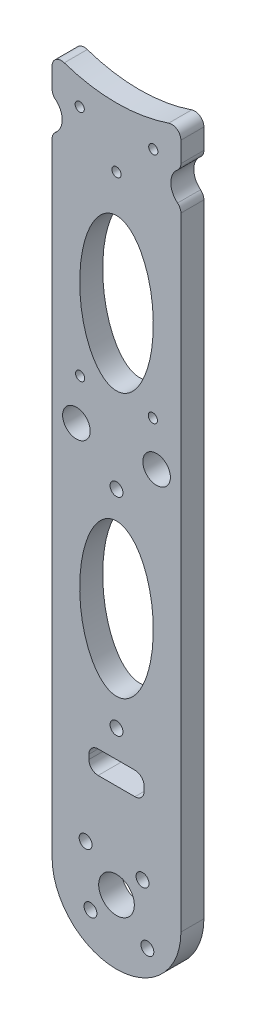
SolidWorks part; units mm, degrees
ref_plane "Front Plane" through (0, 0, 0) normal (0, 0, 1) x (1, 0, 0)
ref_plane "Top Plane" through (0, 0, 0) normal (0, 1, 0) x (1, 0, 0)
ref_plane "Right Plane" through (0, 0, 0) normal (1, 0, 0) x (0, 0, -1)
sketch "Sketch1" plane through (0, 0, 0) normal (0, 0, 1) x (1, 0, 0)
  line L0 (-14, 0) -> (-14, 135.3474)
  line L1 (0, 149.0732) -> (0, -14) construction
  line L2 (14, 0) -> (14, 135.3474)
  line L3 (-14, 0) -> (14, 0) construction
  line L4 (-6.7175, 6.7175) -> (6.7175, -6.7175) construction
  line L6 (-9.9779, -9.9779) -> (8.2462, 8.2462) construction
  line L7 (-14, 144.6611) -> (-14, 149.0732)
  line L8 (-4, 20.4839) -> (4, 20.4839)
  line L9 (-6, 22.4839) -> (-6, 23.4839)
  line L10 (-4, 25.4839) -> (4, 25.4839)
  line L11 (6, 22.4839) -> (6, 23.4839)
  line L12 (-6, 20.4839) -> (6, 25.4839) construction
  line L13 (-6, 25.4839) -> (6, 20.4839) construction
  line L14 (14, 144.6611) -> (14, 149.0732)
  arc A0 (-14, 0) -> (14, 0) centre (0, 0) ccw
  arc A1 (-11.3514, 150.9651) -> (11.3514, 150.9651) centre (0, 184.0732) ccw
  circle A2 centre (-8, 144.3712) radius 1
  circle A3 centre (6.7175, -6.7175) radius 1.4
  circle A4 centre (-5.6569, -5.6569) radius 1.4
  circle A5 centre (5.6569, 5.6569) radius 1.4
  circle A6 centre (-6.7175, 6.7175) radius 1.4
  circle A7 centre (8, 144.3712) radius 1
  circle A8 centre (0, 136.0732) radius 1
  circle A9 centre (0, 136.0732) radius 1 construction
  circle A10 centre (-8, 144.3712) radius 1 construction
  circle A11 centre (8, 144.3712) radius 1 construction
  circle A12 centre (7.9033, 93.7383) radius 1
  circle A13 centre (0, 184.0732) radius 35 construction
  circle A16 centre (7.9033, 93.7383) radius 1 construction
  circle A17 centre (0, 31.3839) radius 1.4
  circle A18 centre (0, 76.3839) radius 1.4
  circle A20 centre (8.7156, 84.4537) radius 3
  circle A21 centre (8.7156, 84.4537) radius 1.45 construction
  arc A22 (6, 22.4839) -> (4, 20.4839) centre (4, 22.4839) cw
  arc A23 (4, 25.4839) -> (6, 23.4839) centre (4, 23.4839) cw
  arc A24 (-4, 25.4839) -> (-6, 23.4839) centre (-4, 23.4839) ccw
  arc A25 (-6, 22.4839) -> (-4, 20.4839) centre (-4, 22.4839) ccw
  arc A26 (-14, 149.0732) -> (-11.3514, 150.9651) centre (-12, 149.0732) cw
  arc A27 (11.3514, 150.9651) -> (14, 149.0732) centre (12, 149.0732) cw
  arc A28 (-13.2731, 143.1186) -> (-13.2731, 136.8899) centre (-15.8435, 140.0042) cw
  arc A29 (13.2731, 143.1186) -> (13.2731, 136.8899) centre (15.8435, 140.0042) ccw
  arc A30 (14, 135.3474) -> (13.2731, 136.8899) centre (12, 135.3474) ccw
  arc A31 (13.2731, 143.1186) -> (14, 144.6611) centre (12, 144.6611) ccw
  arc A32 (-14, 144.6611) -> (-13.2731, 143.1186) centre (-12, 144.6611) ccw
  arc A33 (-13.2731, 136.8899) -> (-14, 135.3474) centre (-12, 135.3474) ccw
  circle A34 centre (-7.9033, 93.7383) radius 1
  circle A35 centre (-8.7156, 84.4537) radius 3
  ellipse E0 centre (0, 53.8839) end of major axis (0, 70.3839) minor radius 8
  ellipse E1 centre (0, 111.3839) end of major axis (0, 127.8839) minor radius 8
  point P43 (0, 22.9839)
  point P82 (-14, 151.9952)
  point P85 (14, 151.9952)
  point P94 (14, 136.4115)
  point P97 (14, 143.597)
  point P100 (-14, 143.597)
  point P103 (-14, 136.4115)
  dimension "D3" = 14
  dimension "D5" = 2
  dimension "D2" = 2
  dimension "D4" = 12
  dimension "D8" = 35
  dimension "D10" = 22.5
  dimension "D11" = 9.5
  dimension "D7" = 2.8
  dimension "D15" = 2
  dimension "D16" = 2
  dimension "D18" = 2.8
  dimension "D19" = 9.5
  dimension "D20" = 8
  dimension "D6" = 5
  dimension "D9" = 45
  dimension "D12" = 8
  dimension "D13" = 8
  dimension "D14" = 35
  dimension "D17" = 8
  dimension "D21" = 8.4
extrude "Boss-Extrude1" add sketch "Sketch1" along normal blind 5
sketch "Sketch2" plane through (0, 0, 5) normal (0, 0, 1) x (1, 0, 0)
  circle A0 centre (0, 0) radius 3.875
extrude "Cut-Extrude1" cut sketch "Sketch2" against normal up to next
